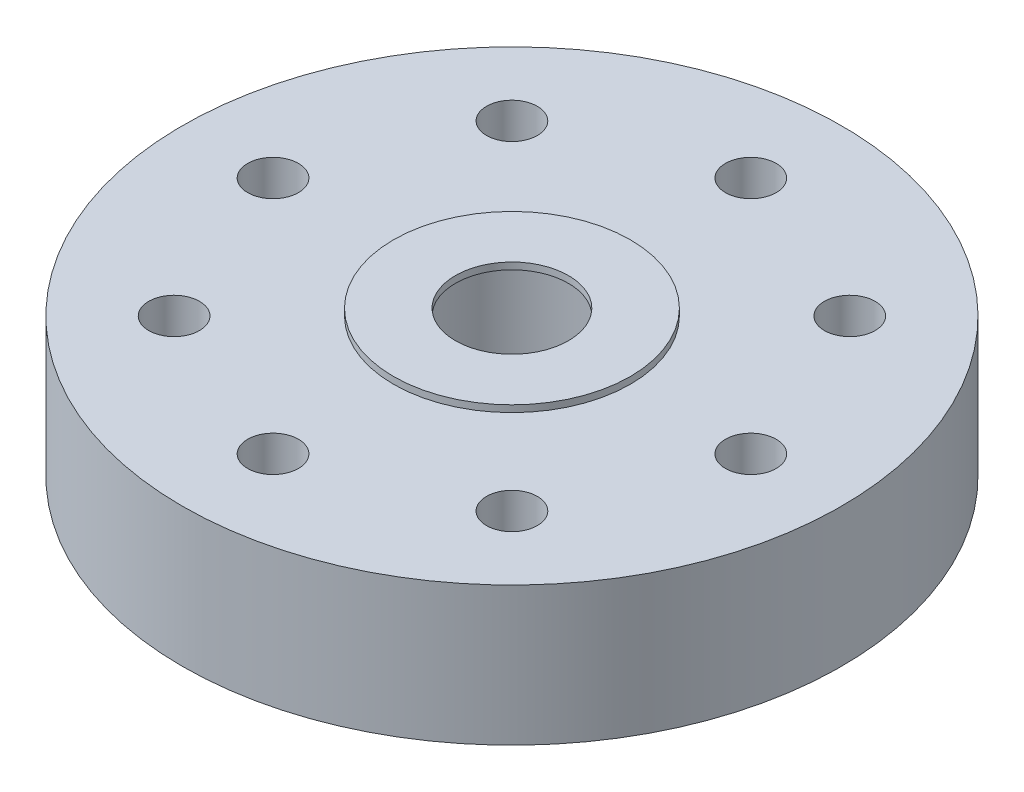
SolidWorks part; units mm, degrees
ref_plane "Front Plane" through (0, 0, 0) normal (0, 0, 1) x (1, 0, 0)
ref_plane "Top Plane" through (0, 0, 0) normal (0, 1, 0) x (1, 0, 0)
ref_plane "Right Plane" through (0, 0, 0) normal (1, 0, 0) x (0, 0, -1)
sketch "Sketch1" plane through (0, 0, 0) normal (0, 1, 0) x (1, 0, 0)
  circle A0 centre (0, 0) radius 9.74
  circle A2 centre (0, 0) radius 2.57
  dimension "D1" = 5.14
  dimension "D2" = 19.48
extrude "MountBody" add sketch "Sketch1" along normal blind 4.1
sketch "Sketch2" plane through (0, 4.1, 0) normal (0, 1, 0) x (1, 0, 0)
  circle A0 centre (0, 0) radius 3.5
  circle A1 centre (0, 0) radius 1.67
  point P5 (0, 0)
  dimension "D1" = 3.34
  dimension "D2" = 7
extrude "Cap" add sketch "Sketch2" along normal blind 0.2
sketch "Sketch3" plane through (0, 4.1, 0) normal (0, 1, 0) x (1, 0, 0)
  circle A0 centre (7.06, 0) radius 0.75
  circle A3 centre (4.9922, -4.9922) radius 0.75
  circle A4 centre (0, -7.06) radius 0.75
  circle A5 centre (-4.9922, -4.9922) radius 0.75
  circle A6 centre (-7.06, 0) radius 0.75
  circle A7 centre (-4.9922, 4.9922) radius 0.75
  circle A8 centre (0, 7.06) radius 0.75
  circle A9 centre (4.9922, 4.9922) radius 0.75
  point P2 (0, 0)
  point P3 (0, 0)
  point P19 (0, 0)
  dimension "D1" = 1.5
  dimension "D2" = 8
  dimension "D3" = 7.06
extrude "ScrewHoles" cut sketch "Sketch3" against normal through all
